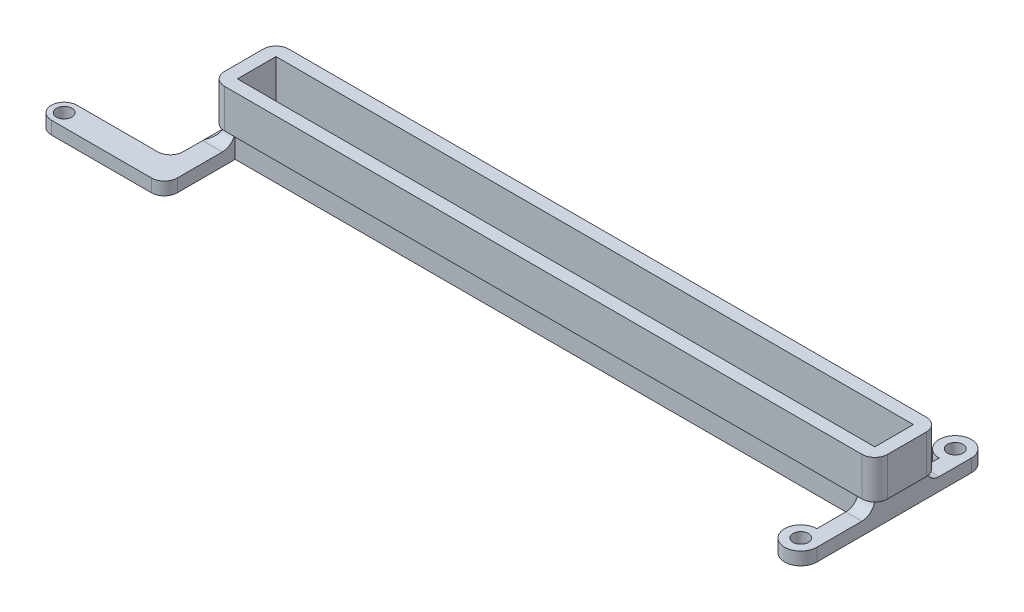
SolidWorks part; units mm, degrees
ref_plane "Front Plane" through (0, 0, 0) normal (0, 0, 1) x (1, 0, 0)
ref_plane "Top Plane" through (0, 0, 0) normal (0, 1, 0) x (1, 0, 0)
ref_plane "Right Plane" through (0, 0, 0) normal (1, 0, 0) x (0, 0, -1)
sketch "Sketch1" plane through (0, 0, 0) normal (0, 1, 0) x (1, 0, 0)
  line L0 (-50.5, 4) -> (-50.5, -4)
  line L1 (-49.5, 3) -> (49.5, 3)
  line L2 (-49.5, 3) -> (-49.5, -3)
  line L3 (-49.5, -3) -> (49.5, -3)
  line L4 (49.5, 3) -> (49.5, -3)
  line L5 (-49.5, 3) -> (49.5, -3) construction
  line L6 (-49.5, -3) -> (49.5, 3) construction
  line L7 (-50.5, -4) -> (50.5, -4)
  line L8 (50.5, 4) -> (50.5, -4)
  line L9 (-50.5, 4) -> (50.5, 4)
  point P0 (0, 0)
  dimension "D1" = 6
  dimension "D2" = 99
  dimension "D3" = 1
extrude "Boss-Extrude1" add sketch "Sketch1" along normal blind 10
sketch "Sketch2" plane through (0, 0, 0) normal (0, -1, 0) x (1, 0, 0)
  line L0 (0, 0) -> (74.3491, 0) construction
  line L1 (48, 0) -> (48, 10.5) construction
  line L2 (50.5, 4) -> (50.5, -4) construction
  line L4 (50.5, 4) -> (67.4224, 4) construction
  line L5 (50.5, -4) -> (69.4178, -4) construction
  line L7 (48, 4) -> (50.5, 4)
  line L9 (48, -4) -> (50.5, -4)
  line L11 (48, 0) -> (48, -8.5) construction
  line L15 (50.5, 4) -> (50.5, 13)
  line L16 (50.5, 13) -> (50, 13) construction
  line L17 (50.5, -4) -> (50.5, -11)
  line L18 (50.5, -11) -> (50, -11) construction
  line L19 (48, 10.5) -> (48, 4)
  line L20 (48, -8.5) -> (48, -4)
  line L21 (-50.5, 4) -> (-50.5, 13) construction
  line L22 (-50.5, 13) -> (-64.4, 13) construction
  line L23 (-66.4, 15) -> (-48.8351, 15)
  line L24 (-48.8351, 15) -> (-48.8351, 4)
  line L25 (-50.5, 4) -> (50.5, 4) construction
  line L26 (-66.4, 11) -> (-51.9017, 11)
  line L27 (-50.5, -4) -> (-59.3527, -4) construction
  line L28 (-51.9017, 11) -> (-51.9017, -4)
  line L29 (-51.9017, -4) -> (-50.5, -4)
  line L30 (-50.5, -4) -> (-50.5, 4)
  line L31 (-50.5, 4) -> (-48.8351, 4)
  line L32 (-64.4, 13) -> (-65.2, 13) construction
  line L33 (-65.2, 13) -> (-66.4, 13) construction
  line L34 (48, 10.5) -> (48, 11) construction
  line L35 (48, 11) -> (48, 13) construction
  line L36 (48, 11) -> (48, 10.5) construction
  line L37 (48, -8.5) -> (48, -9) construction
  line L38 (48, -9) -> (48, -11) construction
  line L39 (48, -9) -> (48, -8.5) construction
  circle A0 centre (48, 13) radius 1.2
  circle A4 centre (48, -11) radius 1.2
  arc A5 (50.5, -11) -> (48, -8.5) centre (48, -11) ccw construction
  arc A8 (48, 10.5) -> (50.5, 13) centre (48, 13) ccw construction
  circle A10 centre (-66.4, 13) radius 1.2
  arc A11 (-66.4, 15) -> (-66.4, 11) centre (-66.4, 13) ccw
  arc A12 (-64.4, 13) -> (-66.4, 15) centre (-66.4, 13) ccw construction
  arc A13 (-66.4, 11) -> (-64.4, 13) centre (-66.4, 13) ccw construction
  arc A14 (50.5, 13) -> (48, 10.5) centre (48, 13) ccw
  arc A15 (48, -8.5) -> (50.5, -11) centre (48, -11) ccw
  dimension "D3" = 2.4
  dimension "D9" = 2.4
  dimension "D10" = 4
  dimension "D1" = 2.5
  dimension "D2" = 13
  dimension "D5" = 11
  dimension "D7" = 9
  dimension "D8" = 15.9
extrude "Boss-Extrude2" add sketch "Sketch2" against normal blind 2
fillet "Fillet1" radius 2 3 edges at (-50.5, 2, 0) (49.25, 2, -4) (49.25, 2, 4)
fillet "Fillet2" radius 2 1 edges at (-50.3684, 2, 4)
sketch "Sketch3" plane through (0, 10, 0) normal (0, 1, 0) x (1, 0, 0)
  line L0 (51.5, 5) -> (-51.5, 5)
  line L1 (-51.5, 5) -> (-51.5, -5)
  line L2 (-51.5, -5) -> (51.5, -5)
  line L3 (51.5, -5) -> (51.5, 5)
  line L4 (50.5, 4) -> (-50.5, 4)
  line L5 (-50.5, 4) -> (-50.5, -4)
  line L6 (-50.5, -4) -> (50.5, -4)
  line L7 (50.5, -4) -> (50.5, 4)
  line L8 (50.5, 4) -> (-50.5, 4)
  line L9 (-50.5, 4) -> (-50.5, -4)
  line L10 (-50.5, -4) -> (50.5, -4)
  line L11 (50.5, -4) -> (50.5, 4)
  dimension "D1" = 0
  dimension "D2" = 1
extrude "Boss-Extrude3" add sketch "Sketch3" against normal blind 6
fillet "Fillet3" radius 2 7 edges at (48, 2, -4) (-51.9017, 1, 11) (-48.8351, 1, 15) (-51.5, 7, -5) (51.5, 7, -5) (51.5, 7, 5) (-51.5, 7, 5)
